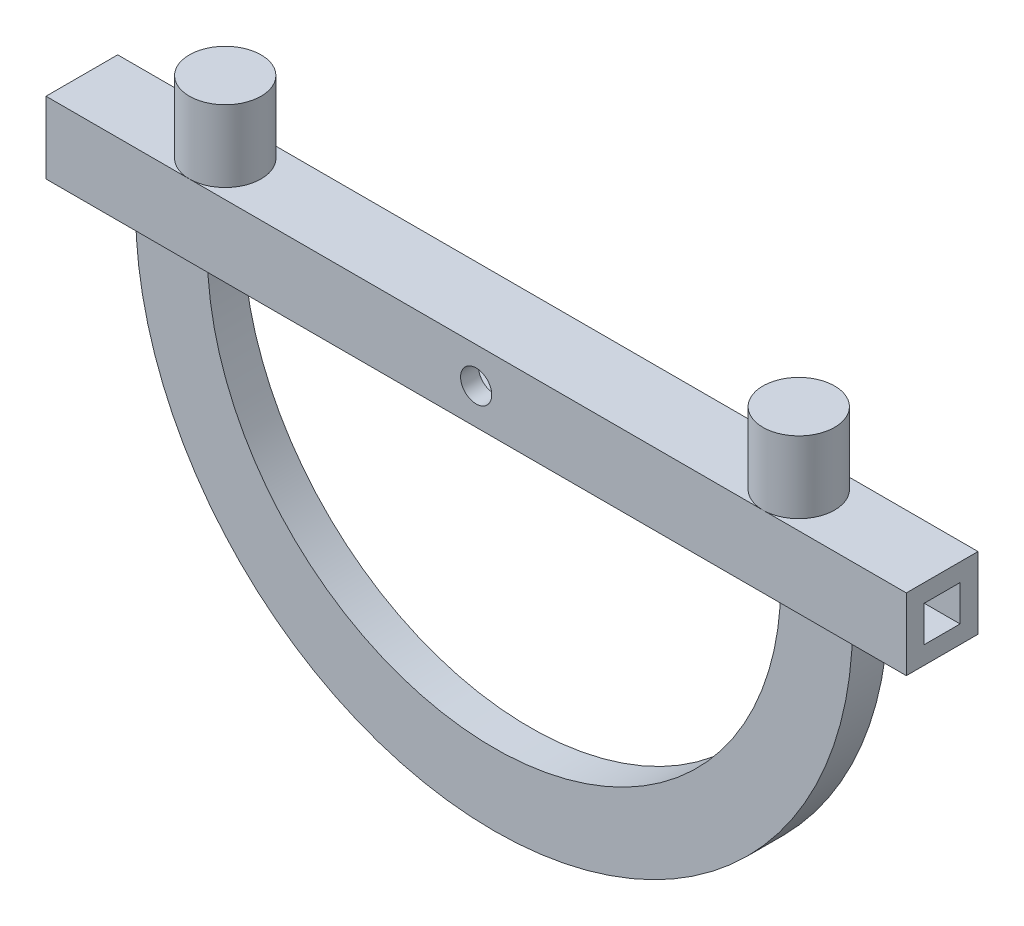
SolidWorks part; units mm, degrees
ref_plane "Plan de face" through (0, 0, 0) normal (0, 0, 1) x (1, 0, 0)
ref_plane "Plan de dessus" through (0, 0, 0) normal (0, 1, 0) x (1, 0, 0)
ref_plane "Plan de droite" through (0, 0, 0) normal (1, 0, 0) x (0, 0, -1)
sketch "Esquisse1" plane through (0, 0, 0) normal (0, 0, 1) x (1, 0, 0)
  line L0 (0, 0) -> (0, -150.9172) construction
  line L1 (0, 0) -> (-178.7051, 0) construction
  line L2 (0, 0) -> (189.7444, 0) construction
  line L3 (-100, 0) -> (-80, 0)
  line L4 (80, 0) -> (100, 0)
  arc A0 (-100, 0) -> (100, 0) centre (0, 0) ccw
  arc A1 (-80, 0) -> (80, 0) centre (0, 0) ccw
  dimension "D1" = 100
  dimension "D4" = 20
  dimension "D2" = 90
  dimension "D3" = 90
extrude "Boss.-Extru.1" add sketch "Esquisse1" along normal blind 5 and the other way blind 5
sketch "Esquisse2" plane through (0, 0, 0) normal (1, 0, 0) x (0, 0, -1)
  line L0 (5, 0) -> (-5, 0) construction
  line L1 (-10, 20) -> (10, 20)
  line L2 (-10, 20) -> (-10, 0)
  line L3 (-10, 0) -> (10, 0)
  line L4 (10, 20) -> (10, 0)
  line L5 (-10, 20) -> (10, 0) construction
  line L6 (-10, 0) -> (10, 20) construction
  line L7 (5, -100) -> (5, 0) construction
  line L9 (-5, 15) -> (5, 15)
  line L10 (-5, 15) -> (-5, 5)
  line L11 (-5, 5) -> (5, 5)
  line L12 (5, 15) -> (5, 5)
  line L13 (-5, 15) -> (5, 5) construction
  line L14 (-5, 5) -> (5, 15) construction
  point P0 (-2.1022, 0)
  point P11 (0, 10)
  dimension "D1" = 20
  dimension "D2" = 20
  dimension "D3" = 5
  dimension "D4" = 10
extrude "Boss.-Extru.2" add sketch "Esquisse2" along normal blind 120 and the other way blind 120
sketch "Esquisse3" plane through (0, 0, -10) normal (0, 0, -1) x (-1, 0, 0)
  line L0 (120, 0) -> (-120, 0) construction
  line L1 (120, 0) -> (120, 20) construction
  circle A0 centre (0, 10) radius 4.3511
  dimension "D1" = 10
  dimension "D2" = 120
extrude "Enlèv. mat.-Extru.1" cut sketch "Esquisse3" against normal blind 120
sketch "Esquisse4" plane through (0, 20, 0) normal (0, 1, 0) x (1, 0, 0)
  line L0 (-120, 10) -> (120, 10) construction
  line L1 (-120, -10) -> (120, -10) construction
  line L2 (-120, 10) -> (-120, -10) construction
  line L3 (120, 10) -> (120, -10) construction
  circle A0 centre (-80, 0) radius 10
  circle A1 centre (80, 0) radius 10
  point P11 (0, 0)
  dimension "D1" = 40
  dimension "D2" = 40
extrude "Boss.-Extru.3" add sketch "Esquisse4" along normal blind 20
